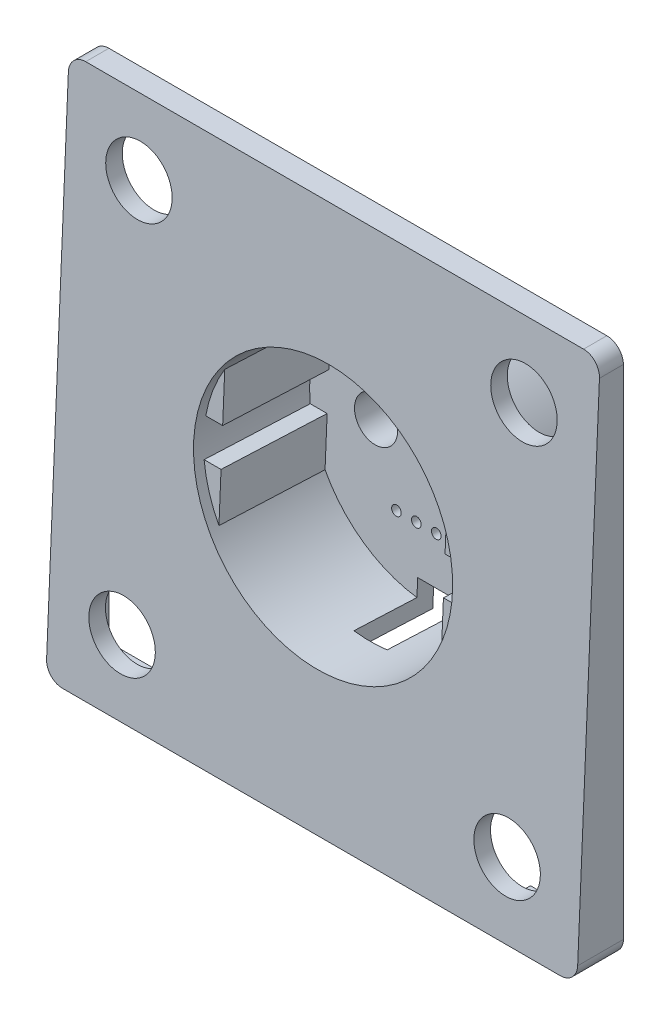
SolidWorks part; units mm, degrees
ref_plane "Ön Düzlem" through (0, 0, 0) normal (0, 0, 1) x (1, 0, 0)
ref_plane "Üst Düzlem" through (0, 0, 0) normal (0, 1, 0) x (1, 0, 0)
ref_plane "Sağ Düzlem" through (0, 0, 0) normal (1, 0, 0) x (0, 0, -1)
sketch "Çizim1" plane through (0, 0, 0) normal (0, 0, 1) x (1, 0, 0)
  line L0 (0, 94.0978) -> (0, -81.5347) construction
  line L1 (-96.2335, 0) -> (117.8421, 0) construction
  line L3 (-37.5, 40) -> (37.5, 40)
  line L4 (-40, 37.5) -> (-40, -37.5)
  line L5 (-37.5, -40) -> (37.5, -40)
  line L6 (40, 37.5) -> (40, -37.5)
  arc A0 (-40, -37.5) -> (-37.5, -40) centre (-37.5, -37.5) ccw
  arc A1 (37.5, -40) -> (40, -37.5) centre (37.5, -37.5) ccw
  arc A2 (37.5, 40) -> (40, 37.5) centre (37.5, 37.5) cw
  arc A3 (-37.5, 40) -> (-40, 37.5) centre (-37.5, 37.5) ccw
  point P17 (-40, 40)
  dimension "D5" = 2.5
  dimension "D1" = 40
  dimension "D2" = 80
  dimension "D3" = 80
  dimension "D4" = 40
extrude "Ekstrüzyon-İnce3" add sketch "Çizim1" along normal blind 7 thin thin type one direction reverse wall 2.5
sketch "Çizim6" plane through (40, 0, 0) normal (1, 0, 0) x (0, 0, -1)
  line L1 (-7, 40) -> (0, 40) construction
  line L2 (-3.5, 40) -> (-7, -40)
  line L3 (-7, -40) -> (-7, 40)
  line L4 (-7, 40) -> (-3.5, 40)
  dimension "D1" = 3.5
extrude "Kes-Ekstrüzyon3" cut sketch "Çizim6" against normal blind 112.5
sketch "Çizim7" plane through (0, 0.2292, 5.24) normal (0, 0.0437, 0.999) x (1, 0, 0)
  line L1 (-38.2758, 38.3418) -> (38.3792, 38.3418)
  line L2 (-38.2758, 38.3418) -> (-38.2758, -38.4901)
  line L3 (-38.2758, -38.4901) -> (38.3792, -38.4901)
  line L4 (38.3792, 38.3418) -> (38.3792, -38.4901)
extrude "Yükseklik-Ekstrüzyon15" add sketch "Çizim7" against normal blind 2.5
sketch "Çizim8" plane through (0, 0.2292, 5.24) normal (0, 0.0437, 0.999) x (1, 0, 0)
  line L0 (0, 29.8509) -> (0, -26.0645) construction
  line L1 (-19.0344, 0) -> (24.7241, 0) construction
  circle A0 centre (0, 0) radius 19.5
  dimension "D1" = 39
extrude "Kes-Ekstrüzyon4" cut sketch "Çizim8" against normal blind 17.5
sketch "Çizim9" plane through (0, 0.2292, 5.24) normal (0, 0.0437, 0.999) x (1, 0, 0)
  circle A0 centre (0, 0) radius 20.75
  dimension "D1" = 41.5
extrude "Yükseklik-Ekstrüzyon16" add sketch "Çizim9" against normal blind 17.5
sketch "Çizim10" plane through (0, 0.2292, 5.24) normal (0, 0.0437, 0.999) x (1, 0, 0)
  circle A0 centre (0, 0) radius 19.5
  dimension "D1" = 39
extrude "Kes-Ekstrüzyon5" cut sketch "Çizim10" against normal blind 17.5
sketch "Çizim11" plane through (0, 0.2292, 5.24) normal (0, 0.0437, 0.999) x (1, 0, 0)
  circle A0 centre (0, 0) radius 20.75
  circle A1 centre (0, 0) radius 19.5
  dimension "D1" = 41.5
  dimension "D2" = 39
extrude "Yükseklik-Ekstrüzyon17" add sketch "Çizim11" along normal blind 1.5
chamfer "Pah1" distance 1.5 angle 45 1 edges at (0, -20.4354, 7.6455)
sketch "Çizim12" plane through (0, -0.5356, -12.2433) normal (0, -0.0437, -0.999) x (-1, 0, 0)
  circle A0 centre (0, 0) radius 20.75
  dimension "D1" = 41.5
extrude "Yükseklik-Ekstrüzyon18" add sketch "Çizim12" along normal blind 2.5
sketch "Çizim13" plane through (0, -0.5356, -12.2433) normal (0, 0.0437, 0.999) x (1, 0, 0)
  line L0 (0, 36.6223) -> (0, -26.6449) construction
  line L1 (7.6552, 0) -> (-11.4827, 0) construction
  circle A0 centre (-9.5, 0) radius 3.25
  circle A1 centre (9.5, 0) radius 3.25
  dimension "D2" = 19
  dimension "D3" = 6.5
  dimension "D4" = 6.5
  dimension "D1" = 9.5
extrude "Kes-Ekstrüzyon7" cut sketch "Çizim13" against normal blind 2.5
sketch "Çizim14" plane through (0, -0.5356, -12.2433) normal (0, 0.0437, 0.999) x (1, 0, 0)
  line L0 (0, 29.0101) -> (0, -24.8666) construction
  line L1 (29.1526, 0) -> (-30.9953, 0) construction
  line L2 (19.2979, 2.8) -> (16.75, 2.8)
  line L3 (16.75, 9.9844) -> (16.75, 2.8)
  line L4 (16.75, -9.9844) -> (16.75, -2.8)
  line L5 (-19.2979, 2.8) -> (-16.75, 2.8)
  line L6 (-16.75, 9.9844) -> (-16.75, 2.8)
  line L7 (19.2979, -2.8) -> (16.75, -2.8)
  line L8 (-16.75, -9.9844) -> (-16.75, -2.8)
  line L9 (-19.2979, -2.8) -> (-16.75, -2.8)
  circle A0 centre (0, 0) radius 19.5
  circle A1 centre (0, 0) radius 19.5 construction
  circle M3 centre (0, 0) radius 19.5
  dimension "D1" = 39
  dimension "D2" = 5.6
  dimension "D4" = 33.5
sketch "Çizim15" plane through (0, -0.5356, -12.2433) normal (0, 0.0437, 0.999) x (1, 0, 0)
  line L0 (0, 34.4478) -> (0, -34.2039) construction
  line L1 (-31.9655, 0) -> (33.3103, 0) construction
  line L2 (2.5, -19.3391) -> (2.5, -16.7891)
  line L3 (-2.5, -16.7891) -> (2.5, -16.7891)
  line L4 (-2.5, 19.3391) -> (-2.5, 16.7891)
  line L5 (-2.5, 16.7891) -> (2.5, 16.7891)
  line L6 (2.5, 19.3391) -> (2.5, 16.7891)
  line L7 (-2.5, -19.3391) -> (-2.5, -16.7891)
  arc A0 (16.75, 9.9844) -> (-16.75, 9.9844) centre (0, 0) ccw construction
  circle A1 centre (0, 0) radius 19.5
  arc M7 (16.75, 9.9844) -> (-16.75, 9.9844) centre (0, 0) ccw
  arc M13 (-16.75, -9.9844) -> (16.75, -9.9844) centre (0, 0) ccw
  dimension "D4" = 39
  dimension "D1" = 2.5
  dimension "D2" = 5
  dimension "D3" = 2.55
extrude "Kes-Ekstrüzyon8" cut sketch "Çizim15" against normal blind 16 contours L6 L4 L5 M7 | L7 L2 L3 M13 region at (0, -18.6365, -11.4514) region at (0, 17.5652, -13.0352)
sketch "Çizim16" plane through (0, -0.6449, -14.7409) normal (0, -0.0437, -0.999) x (-1, 0, 0)
  line L0 (2.5, 16.7891) -> (2.5, 19.3391) construction
  line L1 (-2.5, 16.7891) -> (2.5, 16.7891)
  line L2 (-2.5, 16.7891) -> (-2.5, 21.7891)
  line L3 (-2.5, 21.7891) -> (2.5, 21.7891)
  line L4 (2.5, 16.7891) -> (2.5, 21.7891)
  line L5 (0, 9.913) -> (0, -8.6219) construction
  line L6 (-13.1379, 0) -> (18.1034, 0) construction
  line L7 (-2.5, -16.7891) -> (2.5, -16.7891)
  line L8 (-2.5, -16.7891) -> (-2.5, -21.7891)
  line L9 (-2.5, -21.7891) -> (2.5, -21.7891)
  line L10 (2.5, -16.7891) -> (2.5, -21.7891)
  dimension "D1" = 5
extrude "Kes-Ekstrüzyon10" cut sketch "Çizim16" against normal blind 12
sketch "Çizim17" plane through (0, -0.6449, -14.7409) normal (0, -0.0437, -0.999) x (-1, 0, 0)
  line L0 (0, 10.9316) -> (0, -10.3701) construction
  line L1 (-3.5611, 0) -> (5.2947, 0) construction
  line L3 (-7.5, -8.6891) -> (7.5, -8.6891)
  line L4 (-7.5, -8.6891) -> (-7.5, -11.1891)
  line L5 (-7.5, -11.1891) -> (7.5, -11.1891)
  line L6 (7.5, -8.6891) -> (7.5, -11.1891)
  dimension "D1" = 2.5
  dimension "D2" = 15
  dimension "D3" = 7.5
  dimension "D4" = 5.6
extrude "Yükseklik-Ekstrüzyon21" add sketch "Çizim14" along normal blind 16 contours L6 L5 M3 | L9 L8 M3 | L3 L2 M3 | L7 L4 M3 region at (17.6973, 4.8699, -12.4798) region at (17.6973, -5.9412, -12.0068) region at (-17.6973, 4.8699, -12.4798) region at (-17.6973, -5.9412, -12.0068)
extrude "Kes-Ekstrüzyon14" cut sketch "Çizim17" against normal blind 0.5
sketch "Çizim19" plane through (0, -0.6231, -14.2414) normal (0, -0.0437, -0.999) x (-1, 0, 0)
  line L0 (0, 2.2115) -> (0, -5.0687) construction
  line L2 (-3.7999, 0) -> (16.5883, 0) construction
  line L5 (7.5, -8.6891) -> (-7.5, -8.6891) construction
  line L6 (7.5, -8.6891) -> (-7.5, -8.6891) construction
  circle A0 centre (0, -9.9391) radius 0.725
  circle A1 centre (3, -9.9391) radius 0.725
  circle A2 centre (6, -9.9391) radius 0.725
  circle A3 centre (-3, -9.9391) radius 0.725
  circle A4 centre (-6, -9.9391) radius 0.725
  dimension "D1" = 1.45
  dimension "D3" = 3
  dimension "D5" = 3
  dimension "D6" = 1.25
  dimension "D7" = 3
  dimension "D8" = 1.25
  dimension "D2" = 1.25
  dimension "D4" = 3
extrude "Kes-Ekstrüzyon15" cut sketch "Çizim19" against normal blind 20.5
sketch "Çizim20" plane through (0, -0.6449, -14.7409) normal (0, -0.0437, -0.999) x (-1, 0, 0)
  line L1 (-7.5, -8.6891) -> (7.5, -8.6891)
  line L2 (-7.5, -8.6891) -> (-7.5, -11.1891)
  line L3 (-7.5, -11.1891) -> (7.5, -11.1891)
  line L4 (7.5, -8.6891) -> (7.5, -11.1891)
  line L5 (-8.5, -7.6891) -> (8.5, -7.6891)
  line L6 (-8.5, -7.6891) -> (-8.5, -12.1891)
  line L7 (-8.5, -12.1891) -> (8.5, -12.1891)
  line L8 (8.5, -7.6891) -> (8.5, -12.1891)
  dimension "D1" = 1
  dimension "D2" = 1
  dimension "D3" = 1
  dimension "D4" = 1
extrude "Yükseklik-Ekstrüzyon23" add sketch "Çizim20" along normal blind 1
sketch "Çizim22" plane through (0, -0.6449, -14.7409) normal (0, -0.0437, -0.999) x (-1, 0, 0)
  circle A0 centre (-9.5, 0) radius 4.25
  circle A1 centre (9.5, 0) radius 4.25
  circle A4 centre (-9.5, 0) radius 3.25
  circle A5 centre (9.5, 0) radius 3.25
  dimension "D1" = 8.5
  dimension "D2" = 8.5
  dimension "D3" = 6.5
  dimension "D4" = 6.5
extrude "Yükseklik-Ekstrüzyon26" add sketch "Çizim22" along normal blind 2.5
sketch "Çizim26" plane through (0, -0.6449, -14.7409) normal (0, -0.0437, -0.999) x (-1, 0, 0)
  line L0 (0, 9.3055) -> (0, -4.9493) construction
  line L1 (-2.5955, 0) -> (18.607, 0) construction
  line L2 (-9.5, 3.25) -> (-9.5, 0) construction
  line L3 (9.5, 3.25) -> (9.5, 0) construction
  line L4 (-8, -8.9765) -> (-8, -3.9765)
  line L5 (-10, 9.9765) -> (-9, 9.9765)
  line L6 (-11, 8.9765) -> (-11, 3.9765)
  line L7 (-11, -8.9765) -> (-11, -3.9765)
  line L8 (-8, 8.9765) -> (-8, 3.9765)
  line L9 (-10, -9.9765) -> (-9, -9.9765)
  line L10 (10, -9.9765) -> (9, -9.9765)
  line L11 (8, 8.9765) -> (8, 3.9765)
  line L12 (11, -8.9765) -> (11, -3.9765)
  line L13 (11, 8.9765) -> (11, 3.9765)
  line L14 (10, 9.9765) -> (9, 9.9765)
  line L15 (8, -8.9765) -> (8, -3.9765)
  arc A0 (-10, -9.9765) -> (-11, -8.9765) centre (-10, -8.9765) cw
  arc A1 (-9, -9.9765) -> (-8, -8.9765) centre (-9, -8.9765) ccw
  circle A2 centre (-9.5, 0) radius 4.25
  arc A3 (-9, 9.9765) -> (-8, 8.9765) centre (-9, 8.9765) cw
  arc A4 (-10, 9.9765) -> (-11, 8.9765) centre (-10, 8.9765) ccw
  arc A5 (10, 9.9765) -> (11, 8.9765) centre (10, 8.9765) cw
  arc A6 (9, 9.9765) -> (8, 8.9765) centre (9, 8.9765) ccw
  circle A7 centre (9.5, 0) radius 4.25
  arc A8 (9, -9.9765) -> (8, -8.9765) centre (9, -8.9765) cw
  arc A9 (10, -9.9765) -> (11, -8.9765) centre (10, -8.9765) ccw
  point P22 (-11, 9.9765)
  point P29 (-11, -9.9765)
  point P48 (11, -9.9765)
  point P49 (11, 9.9765)
  circle M1 centre (-9.5, 0) radius 4.25
  line M11 (-8.5, -12.1891) -> (-8.5, -7.6891)
  line M12 (-8.5, -7.6891) -> (8.5, -7.6891)
  line M13 (8.5, -7.6891) -> (8.5, -12.1891)
  circle M14 centre (9.5, 0) radius 4.25
  dimension "D3" = 8.5
  dimension "D5" = 1
  dimension "D1" = 1.5
  dimension "D2" = 3
  dimension "D4" = 6
extrude "Yükseklik-Ekstrüzyon27" add sketch "Çizim26" along normal blind 13 contours L5 A4 L6 L8 A3 M1 | L14 A6 L11 L13 A5 M14 | L10 A9 L12 L15 A8 M14 M12 M13 | L9 A1 L4 L7 A0 M11 M12 M1 region at (-9.5731, -7.5407, -14.4392) region at (9.5731, -7.5407, -14.4392) region at (9.5, 6.3484, -15.0469) region at (-9.5, 6.3484, -15.0469)
sketch "Çizim31" plane through (0, -12.1774, 0.5328) normal (0, -0.999, 0.0437) x (1, 0, 0)
  line L0 (0, 0) -> (0, -22.981) construction
  line L1 (0, -15.755) -> (15.5795, -15.755) construction
  circle A0 centre (0, -15.755) radius 0.725
  circle A1 centre (3, -15.755) radius 0.725
  circle A2 centre (6, -15.755) radius 0.725
  circle A3 centre (-3, -15.755) radius 0.725
  circle A4 centre (-6, -15.755) radius 0.725
  dimension "D1" = 1.45
  dimension "D3" = 3
  dimension "D5" = 3
  dimension "D4" = 3
  dimension "D2" = 3
extrude "Kes-Ekstrüzyon19" cut sketch "Çizim31" against normal blind 5
chamfer "Pah5" distance 1 angle 45 20 edges at (-8, -6.4721, -14.486) (8.7412, -10.5778, -14.3064) (9.5, -10.6119, -14.3049) (11, -7.1152, -14.4578) (10.7071, -10.3193, -14.3177) (8, -6.4721, -14.486) (11, 5.8254, -15.024) (10.7071, 9.0294, -15.1642) (9.5, 9.322, -15.177) (8, 5.8254, -15.024) (8.2929, 9.0294, -15.1642) (-8, 5.8254, -15.024) (-8.2929, 9.0294, -15.1642) (-9.5, 9.322, -15.177) (-10.7071, 9.0294, -15.1642) (-11, 5.8254, -15.024) (-8.7412, -10.5778, -14.3064) (-9.5, -10.6119, -14.3049) (-11, -7.1152, -14.4578) (-10.7071, -10.3193, -14.3177)
ref_plane "Düzlem2" through (0, -37.5, 0) normal (0, 1, 0) x (1, 0, 0)
sketch "Çizim37" plane through (0, -37.5, 0) normal (0, 1, 0) x (1, 0, 0)
  line L0 (0, 0) -> (0, -6.3762) construction
  line L1 (-37.5, 0) -> (37.5, 0) construction
  line L2 (22, 0) -> (18.6341, -3.4753)
  line L3 (-22, 0) -> (-18.6341, -3.4753)
  line L4 (-22, 0) -> (22, 0)
  line L5 (-37.5, -4.3882) -> (37.5, -4.3882) construction
  line L6 (16.4791, -4.3882) -> (-16.4791, -4.3882)
  arc A0 (-18.6341, -3.4753) -> (-16.4791, -4.3882) centre (-16.4791, -1.3882) ccw
  arc A1 (18.6341, -3.4753) -> (16.4791, -4.3882) centre (16.4791, -1.3882) cw
  point P10 (0, -4.3882)
  point P12 (0, 0)
  point P14 (-17.75, -4.3882)
  point P17 (17.75, -4.3882)
  dimension "D3" = 3
  dimension "D1" = 4.25
  dimension "D2" = 22
extrude "Kes-Ekstrüzyon29" cut sketch "Çizim37" against normal blind 21
sketch "Çizim40" plane through (0, -37.5, 0) normal (0, 1, 0) x (1, 0, 0)
  line L0 (16.4791, -4.3882) -> (37.5, -4.3882) construction
  line L1 (26, -4.3882) -> (-26, -4.3882)
  line L2 (26, -4.3882) -> (26, 0)
  line L3 (26, 0) -> (-26, 0)
  line L4 (-26, -4.3882) -> (-26, 0)
  line L5 (-37.5, 0) -> (-22, 0) construction
  line L6 (0, 0.2626) -> (0, 12.1609) construction
  dimension "D1" = 26
  dimension "D2" = 52
extrude "Kes-Ekstrüzyon30" cut sketch "Çizim40" against normal blind 0.9
sketch "Çizim45" plane through (0, 0.12, 2.7424) normal (0, -0.0437, -0.999) x (-1, 0, 0)
  circle A0 centre (0, 0) radius 22
  circle A1 centre (0, 0) radius 20.75
  dimension "D1" = 44
extrude "Yükseklik-Ekstrüzyon31" add sketch "Çizim45" along normal blind 17.5
sketch "Çizim46" plane through (0, -0.6449, -14.7409) normal (0, -0.0437, -0.999) x (-1, 0, 0)
  line L1 (-2.5, 16.7891) -> (2.5, 16.7891)
  line L2 (-2.5, 16.7891) -> (-2.5, 24.6685)
  line L3 (-2.5, 24.6685) -> (2.5, 24.6685)
  line L4 (2.5, 16.7891) -> (2.5, 24.6685)
  line L5 (2.5, 16.7891) -> (2.5, 20.5988) construction
  line L6 (0, 0) -> (-34.6436, 0) construction
  line L8 (2.5, -16.7891) -> (2.5, -24.6685)
  line L9 (-2.5, -24.6685) -> (2.5, -24.6685)
  line L10 (-2.5, -16.7891) -> (-2.5, -24.6685)
  line L11 (-2.5, -16.7891) -> (2.5, -16.7891)
extrude "Kes-Ekstrüzyon32" cut sketch "Çizim46" against normal blind 12
sketch "Çizim47" plane through (0, 0, 0) normal (0, 0, -1) x (-1, 0, 0)
  line L1 (37.5, -40) -> (-37.5, -40) construction
  line L2 (-40, 37.5) -> (-40, -37.5) construction
  circle A0 centre (-29, -29) radius 5
  circle A1 centre (-29, 29) radius 5
  circle A2 centre (29, 29) radius 5
  circle A3 centre (29, -29) radius 5
  point P15 (0, 0)
  dimension "D3" = 10
  dimension "D1" = 11
  dimension "D2" = 11
  dimension "D4" = 4
extrude "Kes-Ekstrüzyon33" cut sketch "Çizim47" against normal blind 24
sketch "Çizim48" plane through (40, 0, 0) normal (1, 0, 0) x (0, 0, -1)
  line L0 (-6.8906, -37.5) -> (-3.6094, 37.5)
  line L1 (-3.6094, 37.5) -> (-15.9676, 37.5)
  line L2 (-15.9676, 37.5) -> (-19.2488, -37.5)
  line L3 (-19.2488, -37.5) -> (-6.8906, -37.5)
extrude "Kes-Ekstrüzyon34" cut sketch "Çizim48" against normal up to vertex up to point (-40, -37.5, 6.8906)
